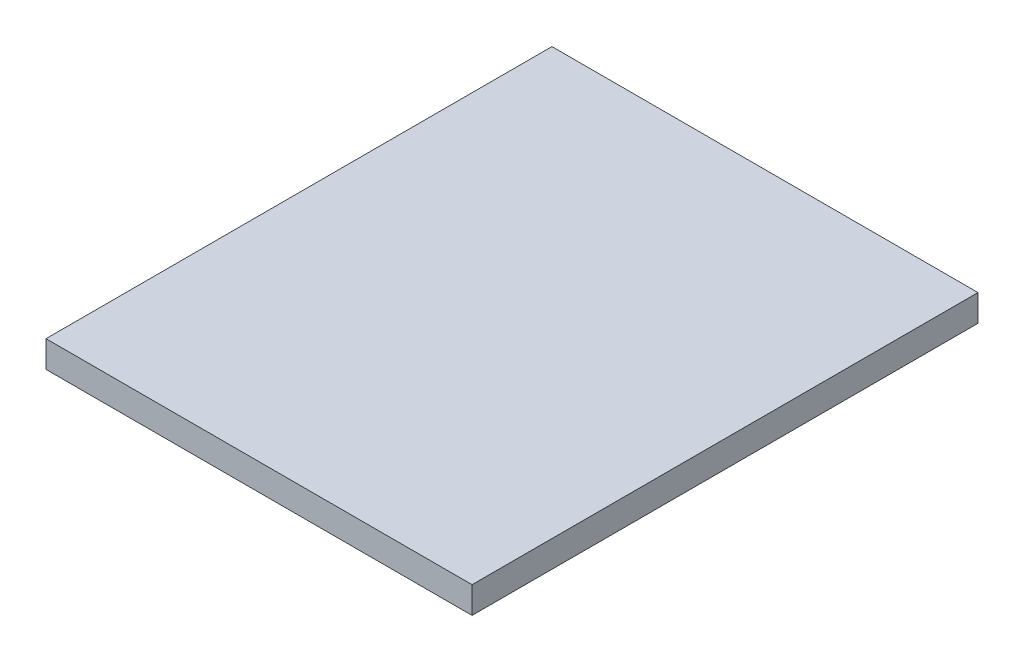
SolidWorks part; units mm, degrees
ref_plane "Front Plane" through (0, 0, 0) normal (0, 0, 1) x (1, 0, 0)
ref_plane "Top Plane" through (0, 0, 0) normal (0, 1, 0) x (1, 0, 0)
ref_plane "Right Plane" through (0, 0, 0) normal (1, 0, 0) x (0, 0, -1)
sketch "Sketch1" plane through (0, 0, 0) normal (0, 1, 0) x (1, 0, 0)
  line L1 (-25.4, 30.1625) -> (25.4, 30.1625)
  line L2 (-25.4, 30.1625) -> (-25.4, -30.1625)
  line L3 (-25.4, -30.1625) -> (25.4, -30.1625)
  line L4 (25.4, 30.1625) -> (25.4, -30.1625)
  line L5 (-25.4, 30.1625) -> (25.4, -30.1625) construction
  line L6 (-25.4, -30.1625) -> (25.4, 30.1625) construction
  point P0 (0, 0)
  dimension "D1" = 50.8
  dimension "D2" = 60.325
extrude "Boss-Extrude1" add sketch "Sketch1" along normal blind 3.175
